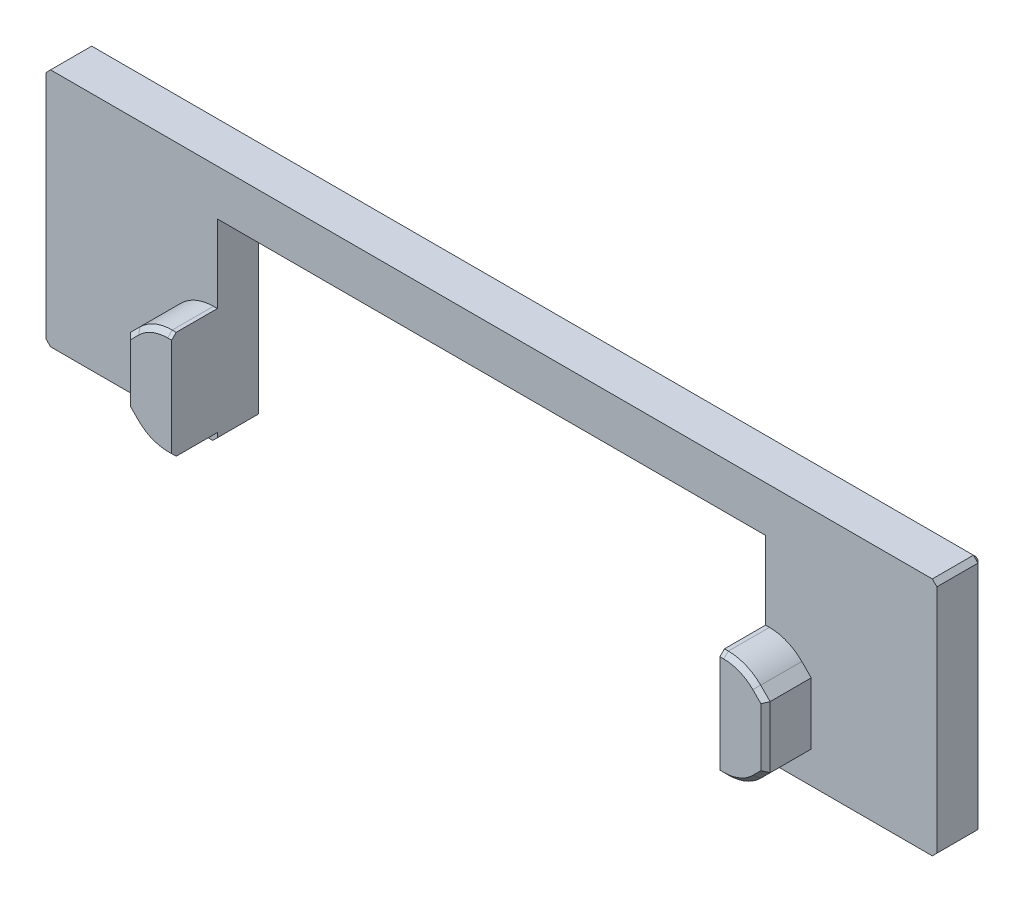
SolidWorks part; units mm, degrees
ref_plane "Front" through (0, 0, 0) normal (0, 0, 1) x (1, 0, 0)
ref_plane "Top" through (0, 0, 0) normal (0, 1, 0) x (1, 0, 0)
ref_plane "Right" through (0, 0, 0) normal (1, 0, 0) x (0, 0, -1)
sketch "Sketch1" plane through (0, 0, 0) normal (0, 0, 1) x (1, 0, 0)
  line L0 (-19.3, 5.25) -> (19.3, 5.25)
  line L5 (19.5, 5.05) -> (19.5, -5.05)
  line L6 (19.3, -5.25) -> (12.2, -5.25)
  line L7 (12, -5.05) -> (12, 3.25)
  line L8 (12, 3.25) -> (-12, 3.25)
  line L9 (-12, 3.25) -> (-12, -5.05)
  line L10 (-12.2, -5.25) -> (-19.3, -5.25)
  line L11 (-19.5, -5.05) -> (-19.5, 5.05)
  line L12 (19.5, 5.05) -> (19.5, -5.05) construction
  line L13 (19.3, -5.25) -> (12, -5.25) construction
  line L14 (19.3, 5.25) -> (-19.3, 5.25) construction
  line L15 (19.5, -5.05) -> (19.3, -5.25)
  line L16 (-12, -5.25) -> (-19.3, -5.25) construction
  line L17 (-19.5, 5.05) -> (-19.5, -5.05) construction
  line L18 (12.2, -5.25) -> (12, -5.05)
  line L19 (19.3, 5.25) -> (19.5, 5.05)
  line L20 (-19.5, 5.05) -> (-19.3, 5.25)
  line L21 (-19.3, -5.25) -> (-19.5, -5.05)
  line L22 (-12, -5.05) -> (-12.2, -5.25)
  point P0 (-19.5, 5.25)
  point P1 (19.5, 5.25)
  point P2 (19.5, -5.25)
  point P4 (12, -5.25)
  point P6 (-19.5, -5.25)
  point P13 (-12, -5.25)
extrude "Boss-Extrude1" add sketch "Sketch1" against normal blind 2
sketch "Sketch3" plane through (0, 0, 0) normal (0, 0, 1) x (1, 0, 0)
  line L3 (12, -5.05) -> (12, 3.25) construction
  line L4 (12, -4.85) -> (12, -0.15)
  line L20 (14, -3.85) -> (14, -1.15)
  line L21 (14, -3.85) -> (14, -1.15)
  line L22 (14, -1.15) -> (13.5858, -0.7358)
  line L23 (14, -1.15) -> (13.5858, -0.7358)
  line L24 (12.1716, -0.15) -> (11.3284, -0.15)
  line L25 (12.1716, -0.15) -> (12, -0.15)
  line L26 (9.9142, -0.7358) -> (9.5, -1.15)
  line L28 (9.5, -1.15) -> (9.5, -3.85)
  line L30 (9.5, -3.85) -> (9.9142, -4.2642)
  line L32 (11.3284, -4.85) -> (12.1716, -4.85)
  line L33 (12, -4.85) -> (12.1716, -4.85)
  line L34 (13.5858, -4.2642) -> (14, -3.85)
  line L35 (13.5858, -4.2642) -> (14, -3.85)
  arc A18 (13.5858, -0.7358) -> (12.1716, -0.15) centre (12.1716, -2.15) ccw
  arc A19 (13.5858, -0.7358) -> (12.1716, -0.15) centre (12.1716, -2.15) ccw
  arc A20 (11.3284, -0.15) -> (9.9142, -0.7358) centre (11.3284, -2.15) ccw
  arc A22 (9.9142, -4.2642) -> (11.3284, -4.85) centre (11.3284, -2.85) ccw
  arc A24 (12.1716, -4.85) -> (13.5858, -4.2642) centre (12.1716, -2.85) ccw
  arc A25 (12.1716, -4.85) -> (13.5858, -4.2642) centre (12.1716, -2.85) ccw
  line M20 (12, 3.25) -> (12, -5.05)
  dimension "D1" = 0
extrude "Boss-Extrude3" add sketch "Sketch3" along normal blind 2 contours L4 | L33 A25 L35 L21 L23 A19 L25 M20 region at (12.92, -2.5, 0)
mirror "Mirror3" about plane through (0, 0, 0) normal (1, 0, 0) of "Boss-Extrude3"
chamfer "Deburs" distance 0.2 angle 45 28 edges at (12, -0.9, -2) (12.1, -5.15, -2) (15.75, -5.25, -2) (19.4, -5.15, -2) (19.5, 0, -2) (19.4, 5.15, -2) (0, 5.25, -2) (-19.4, 5.15, -2) (-19.5, 0, -2) (-19.4, -5.15, -2) (-15.75, -5.25, -2) (-12.1, -5.15, -2) (-12, -0.9, -2) (0, 3.25, -2) (-12.0858, -4.85, 2) (-13.7929, -4.0571, 2) (-12.9369, -4.6978, 2) (-14, -2.5, 2) (-13.7929, -0.9429, 2) (-12.0858, -0.15, 2) (-12.9369, -0.3022, 2) (12.0858, -4.85, 2) (13.7929, -4.0571, 2) (12.9369, -4.6978, 2) (14, -2.5, 2) (13.7929, -0.9429, 2) (12.0858, -0.15, 2) (12.9369, -0.3022, 2)
